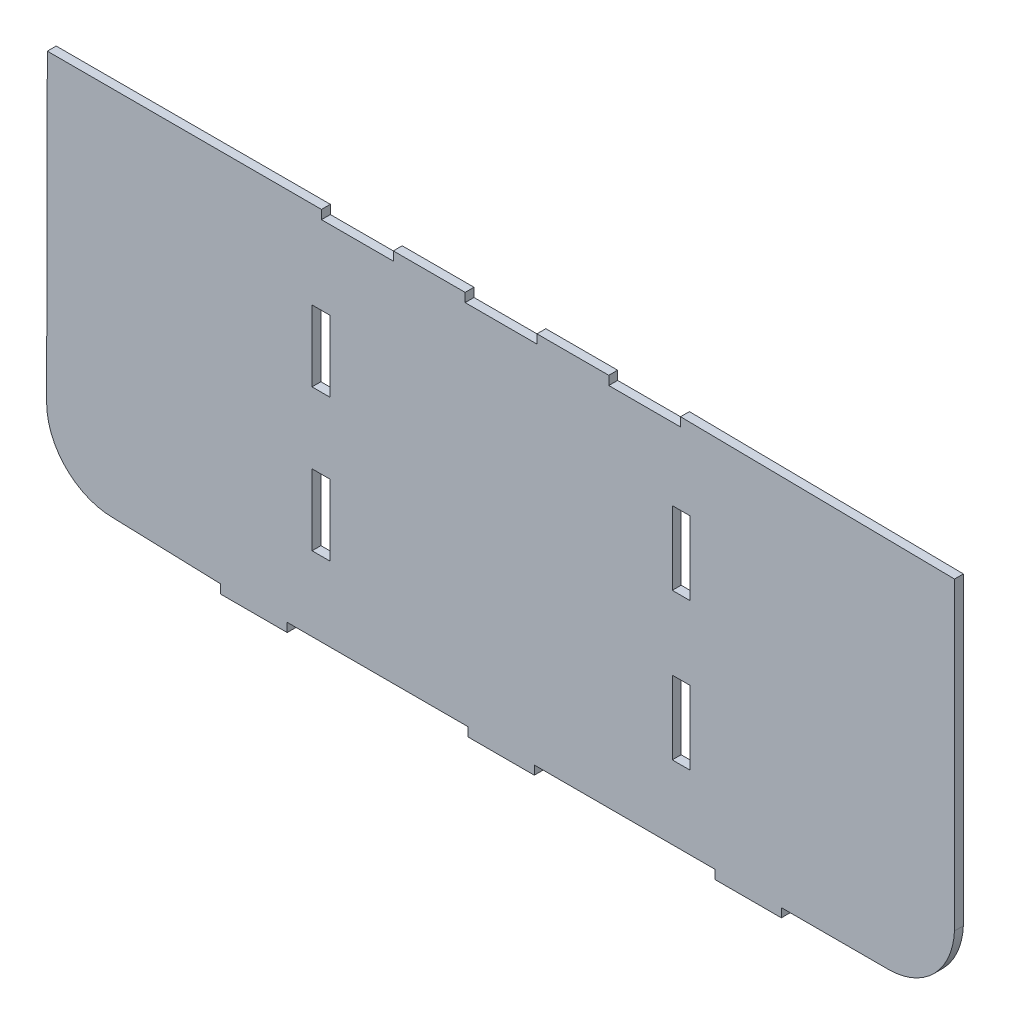
SolidWorks part; units mm, degrees
ref_plane "Front Plane" through (0, 0, 0) normal (0, 0, 1) x (1, 0, 0)
ref_plane "Top Plane" through (0, 0, 0) normal (0, 1, 0) x (1, 0, 0)
ref_plane "Right Plane" through (0, 0, 0) normal (1, 0, 0) x (0, 0, -1)
sketch "Sketch1" plane through (0, 0, 0) normal (0, 0, 1) x (1, 0, 0)
  line L12 (-444.5, 10.16) -> (-321.2, 6.2241)
  line L16 (-245, 6.2241) -> (-38.1, 6.2241)
  line L20 (38.1, 6.2241) -> (245, 6.2241)
  line L27 (205.7064, 435.61) -> (205.558, 425.45)
  line L28 (205.558, 425.45) -> (123.444, 425.45)
  line L29 (123.444, 425.45) -> (123.444, 435.61)
  line L30 (123.444, 435.61) -> (41.148, 435.61)
  line L31 (41.148, 435.61) -> (41.148, 425.45)
  line L32 (41.148, 425.45) -> (-41.148, 425.45)
  line L33 (-41.148, 425.45) -> (-41.148, 435.61)
  line L34 (-41.148, 435.61) -> (-123.444, 435.61)
  line L35 (-123.444, 435.61) -> (-123.444, 425.45)
  line L36 (-123.444, 425.45) -> (-205.74, 425.45)
  line L37 (-205.74, 425.45) -> (-205.74, 388.35)
  line L38 (-205.74, 388.35) -> (-229.9153, 388.35)
  line L39 (-519.9157, 435.61) -> (-520.7, 86.36)
  line L43 (-38.1, 6.2241) -> (-38.1, -3.9359) construction
  line L45 (38.1, 6.2241) -> (38.1, -3.9359) construction
  line L46 (38.1, 6.2241) -> (38.1, -3.9359)
  line L47 (-38.1, 6.2241) -> (-38.1, -3.9359)
  line L48 (245, 6.2241) -> (245, -3.9359) construction
  line L49 (321.2, 6.2241) -> (321.2, -3.9359) construction
  line L50 (245, 6.2241) -> (245, -3.9359)
  line L51 (321.2, 6.2241) -> (321.2, -3.9359)
  line L52 (-245, 6.2241) -> (-245, -3.9359) construction
  line L53 (-321.2, 6.2241) -> (-321.2, -3.9359) construction
  line L54 (-321.2, 6.2241) -> (-321.2, -3.9359)
  line L55 (-245, 6.2241) -> (-245, -3.9359)
  line L56 (216.5353, 174.4512) -> (216.5353, 90.3376) construction
  line L57 (216.5353, 342.6783) -> (216.5353, 258.5647) construction
  line L58 (216.5353, 174.4512) -> (216.5353, 90.3376)
  line L59 (216.5353, 342.6783) -> (216.5353, 258.5647)
  line L60 (-205.74, 425.45) -> (-205.74, 435.61)
  line L61 (-205.74, 435.61) -> (-519.9157, 435.61)
  line L62 (-216.5353, 172.7939) -> (-216.5353, 91.4769)
  line L63 (-216.5353, 335.4278) -> (-216.5353, 254.1108)
  line L64 (196.2153, 342.6783) -> (196.2153, 258.5647)
  line L65 (-196.2153, 335.4278) -> (-196.2153, 254.1108)
  line L66 (-196.2153, 172.7939) -> (-196.2153, 91.4769)
  line L67 (196.2153, 174.4512) -> (196.2153, 90.3376)
  line L68 (196.2153, 342.6783) -> (216.5353, 342.6783)
  line L69 (-196.2153, 335.4278) -> (-216.5353, 335.4278)
  line L70 (-216.5353, 254.1108) -> (-196.2153, 254.1108)
  line L71 (-196.2153, 172.7939) -> (-216.5353, 172.7939)
  line L72 (-196.2153, 91.4769) -> (-216.5353, 91.4769)
  line L73 (196.2153, 90.3376) -> (216.5353, 90.3376)
  line L74 (216.5353, 174.4512) -> (196.2153, 174.4512)
  line L75 (216.5353, 258.5647) -> (196.2153, 258.5647)
  line L76 (-519.9157, 435.61) -> (-519.9157, 465.8105)
  line L77 (-519.9157, 465.8105) -> (-529.9153, 465.719)
  line L78 (-529.9153, 465.719) -> (-529.9153, 494.219)
  line L79 (-529.9153, 494.219) -> (-229.9153, 494.219)
  line L81 (321.2, -3.9359) -> (245, -3.9359)
  line L82 (38.1, -3.9359) -> (-38.1, -3.9359)
  line L83 (-245, -3.9359) -> (-321.2, -3.9359)
  line L84 (-229.9153, 494.219) -> (-229.9153, 388.35)
  line L85 (519.6021, 82.2641) -> (519.6259, 431.5141) construction
  line L86 (519.6021, 82.2641) -> (519.6259, 431.5141)
  line L87 (444.5, 6.2241) -> (321.2, 6.2241)
  line L88 (-519.9157, 435.61) -> (580.4446, 435.61) construction
  line L89 (-123.444, 425.45) -> (629.1878, 425.45) construction
  line L90 (205.7064, 435.61) -> (519.6259, 431.5141)
  line L91 (-205.74, 435.61) -> (-229.9153, 435.61)
  line L92 (-229.9153, 435.61) -> (-229.9153, 388.35)
  line L94 (-229.9153, 388.35) -> (-205.74, 388.35)
  line L95 (-229.9153, 388.35) -> (-229.9153, 435.61)
  line L96 (-229.9153, 435.61) -> (-205.74, 435.61)
  line L97 (-205.74, 388.35) -> (-205.74, 435.61)
  arc A0 (-520.7, 86.36) -> (-444.5, 10.16) centre (-444.5, 86.36) ccw
  ellipse E3 centre (443.8465, 86.3572) end of major axis (443.8465, 166.4933) minor radius 75.8546 (444.5, 6.2241) -> (519.6021, 82.2641) ccw
  dimension "D2" = 20.32
  dimension "D1" = 28.5
  dimension "D4" = 20.32
  dimension "D5" = 20.32
  dimension "D6" = 20.32
  dimension "D7" = 300
other "AlignGroup1"
extrude "Boss-Extrude1" add sketch "Sketch1" along normal blind 10.16 contours L87 E3 L86 L90 L27 L28 L29 L30 L31 L32 L33 L34 L35 L36 L37 L38 L84 L61 L39 A0 L12 L54 L83 L55 L16 L47 L82 L46 L20 L50 L81 L51 L59 L75 L64 L68 L66 L72 L62 L71 L70 L63 L69 L65 L74 L58 L73 | L61 L84 L38 L37 L60 region at (0.0129, 219.1864, 0) region at (-217.8276, 411.98, 0)
